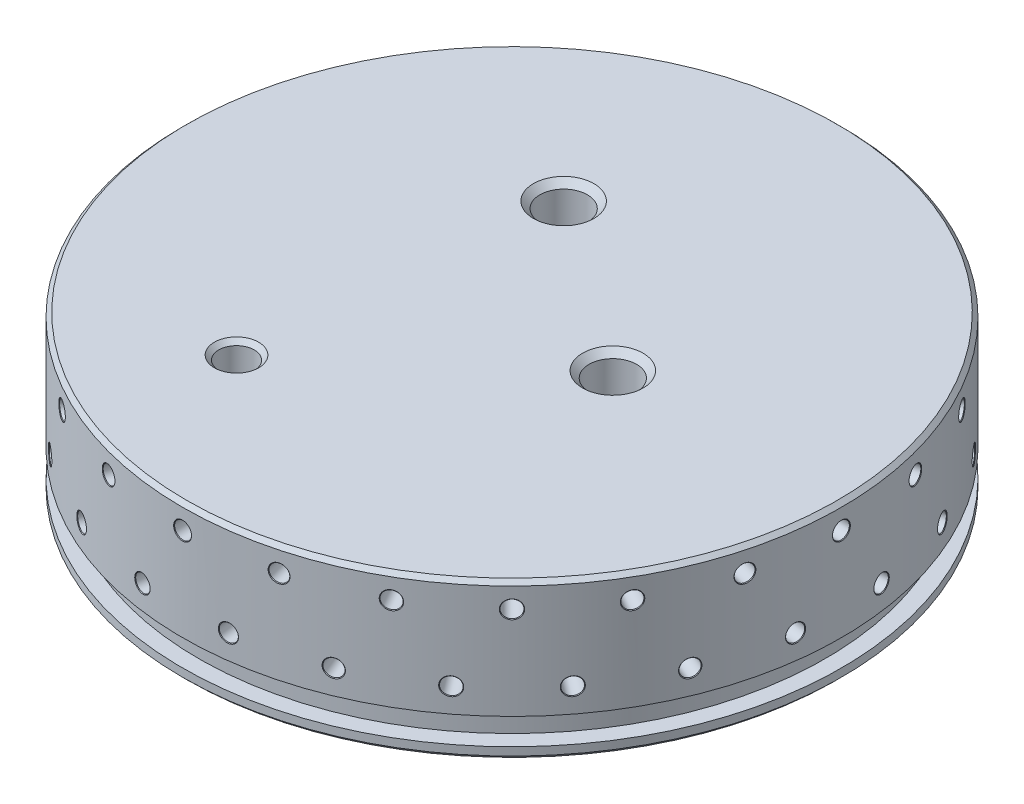
SolidWorks part; units mm, degrees
material "AW-6082-T6 (PA4)"
ref_plane "Płaszczyzna przednia" through (0, 0, 0) normal (0, 0, 1) x (1, 0, 0)
ref_plane "Płaszczyzna górna" through (0, 0, 0) normal (0, 1, 0) x (1, 0, 0)
ref_plane "Płaszczyzna prawa" through (0, 0, 0) normal (1, 0, 0) x (0, 0, -1)
sketch "Szkic1" plane through (0, 0, 0) normal (0, 1, 0) x (1, 0, 0)
  circle A0 centre (0, 0) radius 81.7
  dimension "D1" = 163.4
extrude "Dodanie-wyciągnięcie1" add sketch "Szkic1" along normal blind 38.5
ref_plane "Płaszczyzna1" through (0, 0, -81.7) normal (0, 0, -1) x (-1, 0, 0)
ref_plane "Płaszczyzna2" through (10.664, 0, -81.001) normal (0.1305, 0, -0.9914) x (0, -1, 0)
hole_wizard "Otwór gwintowany M51" positions "Szkic2" profile "Szkic3" hole size "M5" standard "ISO"
sketch "Szkic2" plane through (0, 0, -81.7) normal (0, 0, -1) x (-1, 0, 0)
  line L0 (81.7, 0) -> (81.7, 38.5) construction
  line L1 (-81.7, 38.5) -> (-81.7, 0) construction
  line L2 (81.7, 0) -> (81.7, 38.5)
  line L3 (-81.7, 38.5) -> (-81.7, 0)
  line L4 (0, 51.4702) -> (0, -13.4001) construction
  line L5 (81.7, 38.5) -> (-81.7, 38.5) construction
  point P11 (0, 32.5)
  dimension "D1" = 6
sketch "Szkic3" plane through (0, 32.5, -81.7) normal (1, 0, 0) x (0, 1, 0)
  line L0 (0, 0) -> (0, 9.2618)
  line L1 (0, 9.2618) -> (2.1, 8)
  line L2 (2.1, 8) -> (2.1, 0.15)
  line L3 (2.1, 0.15) -> (2.25, 0)
  line L5 (2.25, 0) -> (0, 0)
  line L6 (-2.1, 0.15) -> (-2.25, 0) construction
  line L10 (0, 9.2618) -> (-2.1, 8) construction
  line L11 (0, -6.35) -> (0, 107.95) construction
  dimension "Średnica otworu" = 4.2
  dimension "Głębokośc otworu" = 8
  dimension "Średnica zewnętrznego pogłębienia stożkowego" = 4.5
  dimension "Kąt zewnętrznego pogłębienia stożkowego" = 90
  dimension "Kąt wiertła" = 118
hole_wizard "Otwór gwintowany M52" positions "Szkic6" profile "Szkic7" hole size "M5" standard "ISO"
sketch "Szkic6" plane through (10.664, 0, -81.001) normal (0.1305, 0, -0.9914) x (0, -1, 0)
  line L0 (-38.5, -81.7) -> (0, -81.7) construction
  line L1 (0, 81.7) -> (-38.5, 81.7) construction
  line L2 (-38.5, -81.7) -> (0, -81.7)
  line L3 (0, 81.7) -> (-38.5, 81.7)
  line L4 (-54.6249, 0) -> (16.9218, 0) construction
  ellipse E0 centre (-32.5, 10.6444) end of major axis (-30.4, 10.6444) minor radius 2.082 construction
  point P10 (-15.5, 0)
  dimension "D1" = 17
sketch "Szkic7" plane through (10.664, 15.5, -81.001) normal (0, 1, 0) x (-0.9914, 0, -0.1305)
  line L0 (0, 0) -> (0, 9.2618)
  line L1 (0, 9.2618) -> (2.1, 8)
  line L2 (2.1, 8) -> (2.1, 0.15)
  line L3 (2.1, 0.15) -> (2.25, 0)
  line L5 (2.25, 0) -> (0, 0)
  line L6 (-2.1, 0.15) -> (-2.25, 0) construction
  line L10 (0, 9.2618) -> (-2.1, 8) construction
  line L11 (0, -6.35) -> (0, 107.95) construction
  dimension "Średnica otworu" = 4.2
  dimension "Głębokośc otworu" = 8
  dimension "Średnica zewnętrznego pogłębienia stożkowego" = 4.5
  dimension "Kąt zewnętrznego pogłębienia stożkowego" = 90
  dimension "Kąt wiertła" = 118
pattern_circular "Szyk kołowy1" count 24 over 360 about axis through (0, 38.5, 0) along (0, -1, 0) of "Otwór gwintowany M51", "Otwór gwintowany M52"
sketch "Szkic8" plane through (0, 0, 0) normal (0, 0, 1) x (1, 0, 0)
  line L0 (-81.7, 30.25) -> (-81.7, 0) construction
  line L1 (-81.7, 30.25) -> (-81.7, 0)
  line L2 (-81.7, 0) -> (81.7, 0) construction
  line L3 (-81.7, 9.5) -> (-77.7, 9.5)
  line L4 (-81.7, 9.5) -> (-81.7, 3)
  line L5 (-81.7, 3) -> (-77.7, 3)
  line L6 (-77.7, 9.5) -> (-77.7, 3)
  line L8 (0, 56.0732) -> (0, -20.5484) construction
  line L9 (81.7, 0) -> (81.7, 30.25) construction
  dimension "D1" = 4
  dimension "D2" = 6.5
  dimension "D3" = 3
revolve "Wycięcie-obrót1" cut sketch "Szkic8" angle 360 about L8 region at (-79.7, 6.25, 0)
sketch "Szkic9" plane through (0, 0, 0) normal (0, 0, 1) x (1, 0, 0)
  line L0 (0, -10.2266) -> (0, 51.1756) construction
  line L1 (-81.7, 0) -> (81.7, 0) construction
  line L2 (0, 0) -> (-66.7, 0)
  line L3 (0, 0) -> (0, 23.5)
  line L4 (0, 23.5) -> (-66.7, 23.5)
  line L5 (-66.7, 0) -> (-66.7, 23.5)
  line L6 (-81.7, 30.2501) -> (-81.7, 9.5) construction
  line L7 (-81.7, 30.2501) -> (-81.7, 9.5)
  line L8 (-73.7, 34.6) -> (-73.7, 30.4) construction
  line L9 (81.7, 38.5) -> (-81.7, 38.5) construction
  line L10 (81.7, 38.5) -> (-81.7, 38.5)
  dimension "D1" = 15
  dimension "D2" = 7
  dimension "D3" = 15
revolve "Wycięcie-obrót2" cut sketch "Szkic9" angle 360 about L0 region at (-33.35, 11.75, 0)
chamfer "Sfazowanie1" distance 1 angle 45 3 edges at (0, 0, -66.7) (0, 0, 81.7) (0, 38.5, 81.7)
hole_wizard "Otwór gwintowany G1/41" positions "Szkic10" profile "Szkic11" tap size "G1/4" standard "ISO" end condition up to next
sketch "Szkic10" plane through (0, 38.5, 0) normal (0, 1, 0) x (1, 0, 0)
  line L0 (0, 0) -> (25, 0) construction
  line L3 (0, 0) -> (-17.5, 30.3109) construction
  circle A0 centre (0, 0) radius 35
  circle A1 centre (0, 0) radius 25
  point P0 (-17.5, 30.3109)
  point P2 (25, 0)
  dimension "D1" = 50
  dimension "D2" = 70
  dimension "D3" = 120
sketch "Szkic11" plane through (-17.5, 38.5, -30.3109) normal (1, 0, 0) x (0, 0, 1)
  line L0 (0, 0) -> (0, 15)
  line L1 (0, 15) -> (5.9, 15)
  line L2 (5.9, 15) -> (5.9, 1.6)
  line L3 (5.9, 1.6) -> (7.5, 0)
  line L5 (7.5, 0) -> (0, 0)
  line L6 (-5.9, 1.6) -> (-7.5, 0) construction
  line L11 (0, -6.35) -> (0, 107.95) construction
  dimension "Średnica otworu gwintowanego na wylot" = 11.8
  dimension "Głębokość otworu gwintowanego na wylot" = 15
  dimension "Średnica zewnętrznego pogłębienia stożkowego" = 15
  dimension "Kąt zewnętrznego pogłębienia stożkowego" = 90
cosmetic thread "Gwint otworu1" parameters "D2"=13.157
cosmetic thread "Gwint otworu2" parameters "D2"=13.157
hole_wizard "Otwór gwintowany G1/81" positions "Szkic12" profile "Szkic13" tap size "G1/8" standard "ISO" end condition up to next
sketch "Szkic12" plane through (0, 38.5, 0) normal (0, 1, 0) x (1, 0, 0)
  line L0 (0, 0) -> (-25, -43.3013) construction
  line L5 (0, 0) -> (25, 0) construction
  circle A0 centre (0, 0) radius 50
  point P0 (-25, -43.3013)
  dimension "D1" = 100
  dimension "D2" = 120
sketch "Szkic13" plane through (-25, 38.5, 43.3013) normal (1, 0, 0) x (0, 0, 1)
  line L0 (0, 0) -> (0, 15)
  line L1 (0, 15) -> (4.4, 15)
  line L2 (4.4, 15) -> (4.4, 1.1)
  line L3 (4.4, 1.1) -> (5.5, 0)
  line L5 (5.5, 0) -> (0, 0)
  line L6 (-4.4, 1.1) -> (-5.5, 0) construction
  line L11 (0, -6.35) -> (0, 107.95) construction
  dimension "Średnica otworu gwintowanego na wylot" = 8.8
  dimension "Głębokość otworu gwintowanego na wylot" = 15
  dimension "Średnica zewnętrznego pogłębienia stożkowego" = 11
  dimension "Kąt zewnętrznego pogłębienia stożkowego" = 90
cosmetic thread "Gwint otworu3" parameters "D2"=9.728
